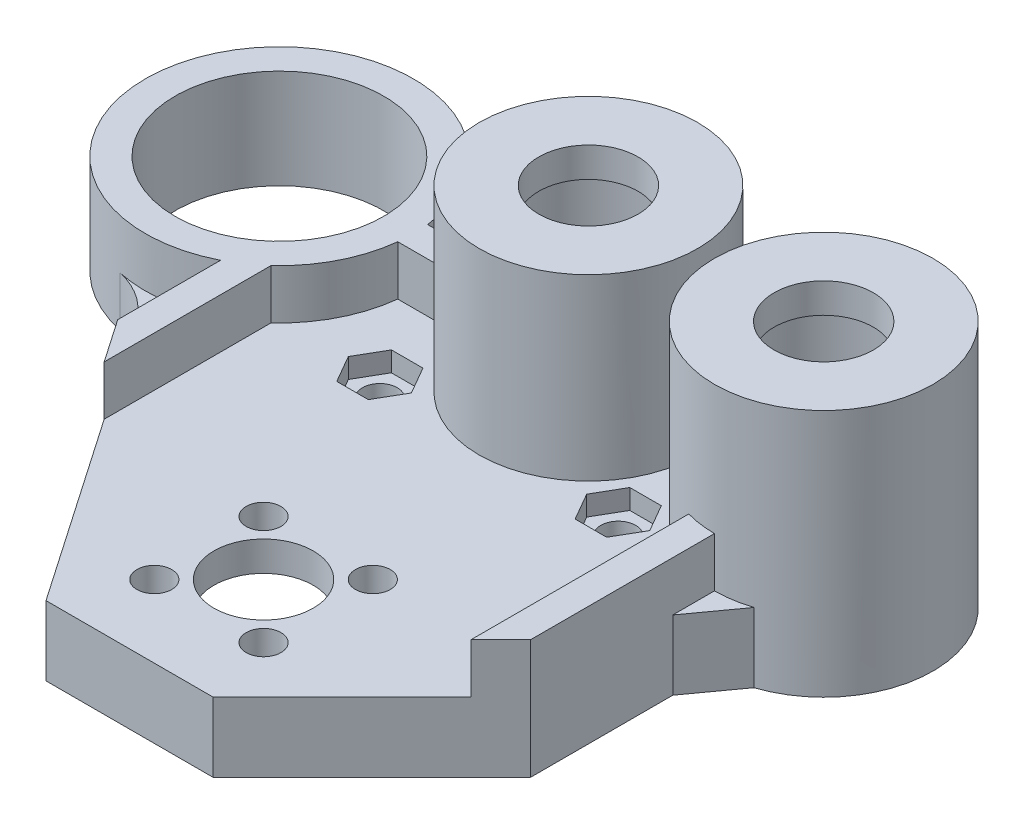
SolidWorks part; units mm, degrees
ref_plane "Front Plane" through (0, 0, 0) normal (0, 0, 1) x (1, 0, 0)
ref_plane "Top Plane" through (0, 0, 0) normal (0, 1, 0) x (1, 0, 0)
ref_plane "Right Plane" through (0, 0, 0) normal (1, 0, 0) x (0, 0, -1)
sketch "Sketch3" plane through (0, 0, 0) normal (0, 1, 0) x (1, 0, 0)
  line L1 (-31.113, 13.5) -> (23.69, 13.5)
  line L2 (-31.113, 13.5) -> (-31.113, -13.5)
  line L3 (-31.113, -13.5) -> (23.69, -13.5)
  line L4 (23.69, 13.5) -> (23.69, -13.5)
  line L5 (23.69, -13.5) -> (-31.113, -13.5)
  line L6 (23.69, -13.5) -> (23.69, -45.5)
  line L7 (23.69, -45.5) -> (-31.113, -45.5)
  line L8 (-31.113, -13.5) -> (-31.113, -45.5)
  circle A0 centre (-31.113, 0) radius 10.5
  circle A1 centre (-31.113, 0) radius 13.5
  circle A2 centre (0, -32.7076) radius 5
  circle A3 centre (0, 0) radius 8
  circle A4 centre (23.69, 0) radius 8
  circle A5 centre (23.69, 0) radius 11
  dimension "D1" = 27
  dimension "D2" = 21
  dimension "D5" = 10
  dimension "D6" = 16
  dimension "D7" = 16
  dimension "D9" = 22
  dimension "D3" = 31.113
  dimension "D4" = 23.69
  dimension "D8" = 23.69
  dimension "D10" = 32
  dimension "D11" = 27
extrude "Boss-Extrude1" add sketch "Sketch3" along normal blind 7 contours L2 A1 A0 | A5 L4 L1 A1 L3 A3 | L2 A1 A0 | L4 A5 A4 | L3 L8 L7 L6 A2 | L4 A5 A4 region at (-21.7805, 0, -9.3325) region at (-3.7115, 0, -12.8891) region at (-31.4149, 0, -12) region at (-3.8855, 0, 29.3496) region at (31.2942, 0, -7.6042) region at (23.444, 0, -9.5)
sketch "Sketch4" plane through (0, 0, 0) normal (0, 1, 0) x (1, 0, 0)
  circle A0 centre (5.5, -27.2076) radius 1.75
  circle A1 centre (0, -32.7076) radius 5 construction
  circle A2 centre (5.5, -38.2076) radius 1.75
  circle A3 centre (-5.5, -38.2076) radius 1.75
  circle A4 centre (-5.5, -27.2076) radius 1.75
  dimension "D3" = 3.5
  dimension "D4" = 3.5
  dimension "D7" = 3.5
  dimension "D9" = 3.5
  dimension "D1" = 5.5
  dimension "D2" = 5.5
  dimension "D5" = 5.5
  dimension "D6" = 5.5
  dimension "D8" = 11
extrude "Cut-Extrude3" cut sketch "Sketch4" along normal through all both and the other way through all
sketch "Sketch6" plane through (0, 7, 0) normal (0, 1, 0) x (1, 0, 0)
  circle A0 centre (23.69, 0) radius 8 construction
  circle A1 centre (0, 0) radius 8 construction
  circle A2 centre (23.69, 0) radius 8
  circle A3 centre (0, 0) radius 8
  circle A4 centre (23.69, 0) radius 11
  circle A5 centre (0, 0) radius 11
  dimension "D1" = 22
extrude "Boss-Extrude2" add sketch "Sketch6" along normal blind 15
sketch "Sketch7" plane through (0, 22, 0) normal (0, 1, 0) x (1, 0, 0)
  circle A0 centre (23.69, 0) radius 11 construction
  circle A1 centre (0, 0) radius 11 construction
  circle A2 centre (23.69, 0) radius 11
  circle A3 centre (0, 0) radius 11
  circle A4 centre (0, 0) radius 5
  circle A5 centre (23.69, 0) radius 5
  dimension "D1" = 10
  dimension "D2" = 10
extrude "Boss-Extrude3" add sketch "Sketch7" along normal blind 3
chamfer "Chamfer1" distance 2.5 angle 45 1 edges at (23.69, 3.5, -11)
sketch "Sketch8" plane through (0, 0, 0) normal (0, 1, 0) x (1, 0, 0)
  line L0 (-31.113, 0) -> (-31.113, 11.75)
  line L1 (-31.113, -13.5) -> (-51.113, -13.5)
  line L2 (-31.113, -13.5) -> (-31.113, 13.5)
  line L3 (-31.113, 13.5) -> (-51.113, 13.5)
  line L4 (-51.113, -13.5) -> (-51.113, 13.5)
  line L5 (-31.113, 11.75) -> (-13.613, 6.5)
  line L6 (-13.613, 6.5) -> (-13.613, -6.5)
  line L7 (-13.613, -6.5) -> (-31.113, -11.75)
  line L8 (-31.113, -11.75) -> (-31.113, 0)
  dimension "D1" = 20
  dimension "D2" = 11.75
  dimension "D3" = 11.75
  dimension "D4" = 27
  dimension "D5" = 17.5
  dimension "D6" = 6.5
  dimension "D7" = 6.5
extrude "Cut-Extrude4" cut sketch "Sketch8" along normal blind 2 contours L4 L1 L2 L0 L3 | L7 L6 L5 L0 L2 region at (-41.113, 0, 0) region at (-23.202, 0, 0)
sketch "Sketch9" plane through (0, 0, 0) normal (0, 1, 0) x (1, 0, 0)
  circle A0 centre (12, 9) radius 1.75
  circle A1 centre (12, -9) radius 1.75
  circle A2 centre (-12, -9) radius 1.75
  circle A3 centre (-12, 9) radius 1.75
  dimension "D3" = 3.5
  dimension "D4" = 3.5
  dimension "D6" = 3.5
  dimension "D8" = 12
  dimension "D9" = 3.5
  dimension "D1" = 12
  dimension "D2" = 9
  dimension "D5" = 9
  dimension "D7" = 12
extrude "Cut-Extrude5" cut sketch "Sketch9" along normal through all both and the other way through all
sketch "Sketch10" plane through (0, 7, 0) normal (0, 1, 0) x (1, 0, 0)
  line L1 (-15.1754, -9) -> (-13.5877, -11.75)
  line L2 (-13.5877, -11.75) -> (-10.4123, -11.75)
  line L3 (-10.4123, -11.75) -> (-8.8246, -9)
  line L4 (-8.8246, -9) -> (-10.4123, -6.25)
  line L5 (-10.4123, -6.25) -> (-13.5877, -6.25)
  line L6 (-13.5877, -6.25) -> (-15.1754, -9)
  line L7 (-15.1754, 9) -> (-13.5877, 6.25)
  line L8 (-13.5877, 6.25) -> (-10.4123, 6.25)
  line L9 (-10.4123, 6.25) -> (-8.8246, 9)
  line L10 (-8.8246, 9) -> (-10.4123, 11.75)
  line L11 (-10.4123, 11.75) -> (-13.5877, 11.75)
  line L12 (-13.5877, 11.75) -> (-15.1754, 9)
  line L13 (15.1754, 9) -> (13.5877, 11.75)
  line L14 (13.5877, 11.75) -> (10.4123, 11.75)
  line L15 (10.4123, 11.75) -> (8.8246, 9)
  line L16 (8.8246, 9) -> (10.4123, 6.25)
  line L17 (10.4123, 6.25) -> (13.5877, 6.25)
  line L18 (13.5877, 6.25) -> (15.1754, 9)
  line L19 (15.1754, -9) -> (13.5877, -6.25)
  line L20 (13.5877, -6.25) -> (10.4123, -6.25)
  line L21 (10.4123, -6.25) -> (8.8246, -9)
  line L22 (8.8246, -9) -> (10.4123, -11.75)
  line L23 (10.4123, -11.75) -> (13.5877, -11.75)
  line L24 (13.5877, -11.75) -> (15.1754, -9)
  circle A0 centre (12, -9) radius 1.75 construction
  circle A1 centre (12, 9) radius 1.75 construction
  circle A2 centre (-12, 9) radius 1.75 construction
  circle A3 centre (-12, -9) radius 1.75 construction
  circle A4 centre (12, -9) radius 1.75
  circle A5 centre (12, 9) radius 1.75
  circle A6 centre (-12, 9) radius 1.75
  circle A7 centre (-12, -9) radius 1.75
  circle A8 centre (-12, -9) radius 2.75 construction
  circle A9 centre (-12, 9) radius 2.75 construction
  circle A10 centre (12, 9) radius 2.75 construction
  circle A11 centre (12, -9) radius 2.75 construction
  dimension "D1" = 5.5
  dimension "D2" = 5.5
  dimension "D3" = 5.5
  dimension "D4" = 5.5
extrude "Cut-Extrude6" cut sketch "Sketch10" against normal blind 2
chamfer "Chamfer2" distance 5 angle 45 1 edges at (23.69, 3.5, 11)
chamfer "Chamfer3" distance 32 distance2 22 1 edges at (-31.113, 3.5, 45.5) first distance on face at (-31.113, 3, 23.5833)
chamfer "Chamfer4" distance 16 angle 45 1 edges at (23.69, 3.5, 45.5)
fillet "Fillet1" radius 8 1 edges at (-31.113, 4.5, 13.5)
sketch "Sketch12" plane through (0, 7, 0) normal (0, 1, 0) x (1, 0, 0)
  line L1 (-19.4184, -1.5) -> (-9.2882, -1.5)
  line L2 (-19.4184, -1.5) -> (-19.4184, 1.5)
  line L3 (-19.4184, 1.5) -> (-9.2882, 1.5)
  line L4 (-9.2882, -1.5) -> (-9.2882, 1.5)
  line L5 (13.6189, -1.5) -> (8.9767, -1.5)
  line L6 (13.6189, -1.5) -> (13.6189, 1.5)
  line L7 (13.6189, 1.5) -> (8.9767, 1.5)
  line L8 (8.9767, -1.5) -> (8.9767, 1.5)
  arc A0 (26.5751, 10.6149) -> (27.1275, -10.4491) centre (23.69, 0) ccw construction
  circle A1 centre (0, 0) radius 11 construction
  circle A2 centre (-31.113, 0) radius 10.5 construction
  arc A3 (26.5751, 10.6149) -> (27.1275, -10.4491) centre (23.69, 0) ccw
  circle A4 centre (0, 0) radius 11
  circle A5 centre (-31.113, 0) radius 10.5
  circle A6 centre (-31.113, 0) radius 13.5
  circle M30 centre (-31.113, 0) radius 10.5
  arc M39 (27.1275, -10.4491) -> (26.5751, 10.6149) centre (23.69, 0) cw
  arc M42 (-31.113, 13.5) -> (-33.9648, -13.1953) centre (-31.113, 0) ccw
  circle M45 centre (0, 0) radius 11
  dimension "D1" = 3
  dimension "D2" = 1.5
extrude "Boss-Extrude4" add sketch "Sketch12" along normal blind 5 contours L7 L5 M39 M45 | A6 L1 L3 M45 | L3 A6 L1 L2 M42 M30 | L1 A6 L3 L2 region at (-18.5295, 7, 0) region at (-18.5575, 7, 1.8812) region at (-14.3033, 7, 0) region at (11.845, 7, 0)
sketch "Sketch13" plane through (0, 7, 0) normal (0, 1, 0) x (1, 0, 0)
  line L0 (23.69, -15.1987) -> (23.69, -29.5) construction
  line L1 (23.69, -15.1987) -> (23.69, -29.5)
  line L3 (23.69, -37.58) -> (20.69, -37.58)
  line L4 (23.69, -37.58) -> (23.69, 1.8154)
  line L5 (23.69, 1.8154) -> (20.69, 1.8154)
  line L6 (20.69, -37.58) -> (20.69, 1.8154)
  line L7 (-22, -2.4764) -> (-25, -2.4764)
  line L8 (-22, -2.4764) -> (-22, -39.8517)
  line L9 (-22, -39.8517) -> (-25, -39.8517)
  line L10 (-25, -2.4764) -> (-25, -39.8517)
  line L17 (-10.8972, -1.5) -> (-17.6966, -1.5)
  line L18 (-29.0625, -16.4826) -> (-9.113, -45.5)
  line L19 (-9.113, -45.5) -> (7.69, -45.5)
  line L20 (7.69, -45.5) -> (23.69, -29.5)
  line L21 (23.69, -29.5) -> (23.69, -15.1987)
  line L22 (23.69, -15.1987) -> (27.1275, -10.4491)
  line L23 (12.7928, -1.5) -> (10.8972, -1.5)
  line L24 (-10.8972, -1.5) -> (-17.6966, -1.5)
  line L25 (-29.0625, -16.4826) -> (-9.113, -45.5)
  line L26 (-9.113, -45.5) -> (7.69, -45.5)
  line L27 (7.69, -45.5) -> (23.69, -29.5)
  line L28 (23.69, -29.5) -> (23.69, -15.1987)
  line L29 (23.69, -15.1987) -> (27.1275, -10.4491)
  line L30 (12.7928, -1.5) -> (10.8972, -1.5)
  arc A4 (-33.9648, -13.1953) -> (-17.6966, -1.5) centre (-31.113, 0) ccw
  arc A5 (-29.0625, -16.4826) -> (-33.9648, -13.1953) centre (-35.6548, -21.0148) ccw
  arc A6 (12.7928, -1.5) -> (27.1275, -10.4491) centre (23.69, 0) ccw
  arc A7 (-10.8972, -1.5) -> (10.8972, -1.5) centre (0, 0) ccw
  arc A8 (-33.9648, -13.1953) -> (-17.6966, -1.5) centre (-31.113, 0) ccw
  arc A9 (-29.0625, -16.4826) -> (-33.9648, -13.1953) centre (-35.6548, -21.0148) ccw
  arc A10 (12.7928, -1.5) -> (27.1275, -10.4491) centre (23.69, 0) ccw
  arc A11 (-10.8972, -1.5) -> (10.8972, -1.5) centre (0, 0) ccw
  arc M39 (-17.6966, -1.5) -> (-33.9648, -13.1953) centre (-31.113, 0) cw
  line M41 (-29.0625, -16.4826) -> (-9.113, -45.5)
  line M43 (7.69, -45.5) -> (23.69, -29.5)
  line M44 (23.69, -29.5) -> (23.69, -15.1987)
  arc M46 (27.1275, -10.4491) -> (12.7928, -1.5) centre (23.69, 0) cw
  dimension "D2" = 3
  dimension "D3" = 3
  dimension "D4" = 22
  dimension "D5" = 0
  dimension "D1" = 0
extrude "Boss-Extrude5" add sketch "Sketch13" along normal blind 5 contours L6 L4 M43 M44 M46 | L10 L8 M39 M41 region at (22.1476, 7, 20.9493) region at (-23.3807, 7, 17.8818)
sketch "Sketch14" plane through (0, 0, 0) normal (0, -1, 0) x (1, 0, 0)
  line L12 (23.69, 15.1987) -> (23.69, 29.5)
  line L13 (23.69, 29.5) -> (7.69, 45.5)
  line L14 (7.69, 45.5) -> (-9.113, 45.5)
  line L15 (-9.113, 45.5) -> (-31.113, 13.5)
  line L16 (-31.113, 13.5) -> (-31.113, 11.75)
  line L17 (-31.113, 11.75) -> (-13.613, 6.5)
  line L18 (-13.613, 6.5) -> (-13.613, -6.5)
  line L19 (-13.613, -6.5) -> (-31.113, -11.75)
  line L20 (-31.113, -11.75) -> (-31.113, -13.5)
  line L21 (-31.113, -13.5) -> (23.69, -13.5)
  line L22 (23.69, -13.5) -> (26.5751, -10.6149)
  line L23 (27.1275, 10.4491) -> (23.69, 15.1987)
  line L24 (23.69, 15.1987) -> (23.69, 29.5)
  line L25 (23.69, 29.5) -> (7.69, 45.5)
  line L26 (7.69, 45.5) -> (-9.113, 45.5)
  line L27 (-9.113, 45.5) -> (-31.113, 13.5)
  line L28 (-31.113, 13.5) -> (-31.113, 11.75)
  line L29 (-31.113, 11.75) -> (-13.613, 6.5)
  line L30 (-13.613, 6.5) -> (-13.613, -6.5)
  line L31 (-13.613, -6.5) -> (-31.113, -11.75)
  line L32 (-31.113, -11.75) -> (-31.113, -13.5)
  line L33 (-31.113, -13.5) -> (23.69, -13.5)
  line L34 (23.69, -13.5) -> (26.5751, -10.6149)
  line L35 (27.1275, 10.4491) -> (23.69, 15.1987)
  circle A0 centre (0, 32.7076) radius 5 construction
  arc A1 (26.5751, -10.6149) -> (27.1275, 10.4491) centre (23.69, 0) ccw
  arc A2 (26.5751, -10.6149) -> (27.1275, 10.4491) centre (23.69, 0) ccw
  circle A3 centre (0, 32.7076) radius 5
  circle A4 centre (0, 32.7076) radius 11.5
  circle M19 centre (0, 32.7076) radius 5
  circle M22 centre (5.5, 27.2076) radius 1.75
  circle M23 centre (5.5, 38.2076) radius 1.75
  circle M24 centre (-5.5, 38.2076) radius 1.75
  circle M25 centre (-5.5, 27.2076) radius 1.75
  dimension "D2" = 23
  dimension "D1" = 0
extrude "Cut-Extrude7" cut sketch "Sketch14" against normal blind 4 contours A4 M19 M23 M25 M24 M22 region at (-11.1747, 0, 32.7076)
